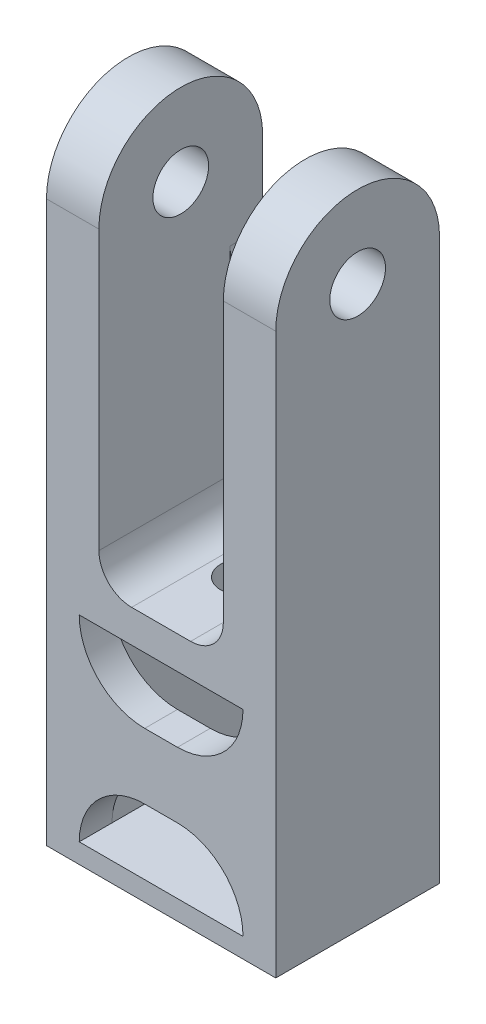
SolidWorks part; units mm, degrees
material "Polybutadiene (PB)"
ref_plane "Front Plane" through (0, 0, 0) normal (0, 0, 1) x (1, 0, 0)
ref_plane "Top Plane" through (0, 0, 0) normal (0, 1, 0) x (1, 0, 0)
ref_plane "Right Plane" through (0, 0, 0) normal (1, 0, 0) x (0, 0, -1)
sketch "Sketch1" plane through (0, 0, 0) normal (0, 0, 1) x (1, 0, 0)
  line L1 (0, 0) -> (35, 0)
  line L2 (0, 0) -> (0, 100)
  line L3 (0, 100) -> (35, 100)
  line L4 (35, 0) -> (35, 100)
  dimension "D1" = 35
  dimension "D2" = 100
extrude "Boss-Extrude1" add sketch "Sketch1" along normal blind 25
sketch "Sketch2" plane through (0, 0, 25) normal (0, 0, 1) x (1, 0, 0)
  line L0 (17.5, 100) -> (17.5, 11.8953) construction
  line L1 (35, 100) -> (0, 100) construction
  line L2 (0, 0) -> (35, 0) construction
  line L3 (8, 160) -> (27, 160)
  line L4 (8, 160) -> (8, 40)
  line L5 (8, 40) -> (27, 40)
  line L6 (27, 160) -> (27, 40)
  line L7 (8, 160) -> (27, 40) construction
  line L8 (8, 40) -> (27, 160) construction
  dimension "D1" = 19
  dimension "D2" = 40
extrude "Cut-Extrude1" cut sketch "Sketch2" against normal blind 25
fillet "Fillet2" 2 edges at (31, 100, 25) (31, 100, 0) type full round first side face at (17.5, 60, 25) second side face at (17.5, 60, 0) middle face at (31, 100, 12.5)
fillet "Fillet3" 2 edges at (4, 100, 25) (4, 100, 0) type full round first side face at (17.5, 56.875, 25) second side face at (17.5, 56.875, 0) middle face at (4, 100, 12.5)
sketch "Sketch3" plane through (0, 0, 0) normal (0, -1, 0) x (1, 0, 0)
  line L0 (35, 12.5) -> (11.8962, 12.5) construction
  line L1 (35, 25) -> (35, 0) construction
  line L2 (11.8962, 12.5) -> (17.5, 0) construction
  line L3 (0, 0) -> (35, 0) construction
  line L4 (17.5, 0) -> (17.5, 13.0424) construction
  circle A0 centre (17.5, 12.5) radius 3.4
  dimension "D1" = 6.8
extrude "Cut-Extrude2" cut sketch "Sketch3" against normal blind 70
sketch "Sketch4" plane through (35, 0, 0) normal (1, 0, 0) x (0, 0, -1)
  line L0 (-12.5, 87.5) -> (-12.5, 43.2819) construction
  arc A0 (0, 87.5) -> (-25, 87.5) centre (-12.5, 87.5) ccw construction
  arc A1 (-12.5, 83.5) -> (-12.5, 83.5) centre (-12.5, 87.5) ccw
  circle A2 centre (-12.5, 87.5) radius 4.25
  point P0 (-12.5, 87.5)
  dimension "D1" = 8.5
extrude "Cut-Extrude3" cut sketch "Sketch4" against normal blind 45 contours A2 region at (35, 87.5, 16.6298) body kept at (8, 87.5001, 0)
sketch "Sketch5" plane through (0, 0, 0) normal (0, 0, -1) x (-1, 0, 0)
  line L0 (-17.5, 40) -> (-17.5, 0) construction
  line L1 (-8, 40) -> (-27, 40) construction
  line L2 (-17.5, 0) -> (0, 20) construction
  line L3 (0, 87.5) -> (0, 0) construction
  line L4 (0, 20) -> (-35, 20) construction
  line L5 (0, 0) -> (-35, 0) construction
  line L6 (-30, 5) -> (-5, 5)
  line L7 (-30, 5) -> (-30, 35)
  line L8 (-30, 35) -> (-5, 35)
  line L9 (-5, 5) -> (-5, 35)
  line L10 (-30, 5) -> (-5, 35) construction
  line L11 (-30, 35) -> (-5, 5) construction
  line L12 (-35, 0) -> (-35, 87.5) construction
  point P8 (-17.5, 20)
  dimension "D1" = 5
  dimension "D2" = 5
  dimension "D3" = 5
extrude "Cut-Extrude4" cut sketch "Sketch5" against normal offset from surface (20 mm away) 5 up to face at (17.5, 53.75, 25)
chamfer "Chamfer1" distance 2 angle 45 4 edges at (35, 0, 12.5) (17.5, 0, 25) (0, 0, 12.5) (17.5, 0, 0)
fillet "Fillet4" radius 5 2 edges at (8, 40, 12.5) (27, 40, 12.5)
sketch "Sketch6" plane through (0, 0, 20) normal (0, 0, -1) x (-1, 0, 0)
  line L0 (-5, 25) -> (-30, 25)
  line L2 (-5, 15) -> (-30, 15)
  line L4 (-5, 5) -> (-5, 35)
  line L5 (-5, 35) -> (-30, 35)
  line L6 (-30, 35) -> (-30, 5)
  line L7 (-30, 5) -> (-5, 5)
  line L8 (-5, 5) -> (-5, 35)
  line L9 (-5, 35) -> (-30, 35)
  line L10 (-30, 35) -> (-30, 5)
  line L11 (-30, 5) -> (-5, 5)
  line M7 (-5, 5) -> (-5, 35)
  line M8 (-5, 35) -> (-30, 35)
  line M9 (-30, 35) -> (-30, 5)
  line M10 (-30, 5) -> (-5, 5)
  dimension "D2" = 10
  dimension "D3" = 10
  dimension "D1" = 0
extrude "Cut-Extrude5" cut sketch "Sketch6" against normal through all contours L0 M7 M8 M9 | L2 M7 M9 M10 region at (17.5, 30, 20) region at (17.5, 10, 20)
fillet "Fillet5" radius 10 4 edges at (30, 15, 22.5) (30, 25, 22.5) (5, 25, 22.5) (5, 15, 22.5)
sketch "Sketch7" plane through (0, 0, 0) normal (0, 0, -1) x (-1, 0, 0)
  line L0 (-8, 66.25) -> (-27, 66.25) construction
  line L1 (-8, 45) -> (-8, 87.5) construction
  line L2 (-27, 45) -> (-27, 87.5) construction
  line L3 (-8, 71.25) -> (-27, 71.25)
  line L4 (-8, 61.25) -> (-27, 61.25)
  line L5 (-8, 71.25) -> (-8, 61.25)
  line L6 (-27, 61.25) -> (-27, 71.25)
  dimension "D1" = 5
  dimension "D2" = 5
extrude "Boss-Extrude2" add sketch "Sketch7" against normal blind 5
fillet "Fillet6" radius 4 4 edges at (8, 71.25, 2.5) (27, 71.25, 2.5) (27, 61.25, 2.5) (8, 61.25, 2.5)
